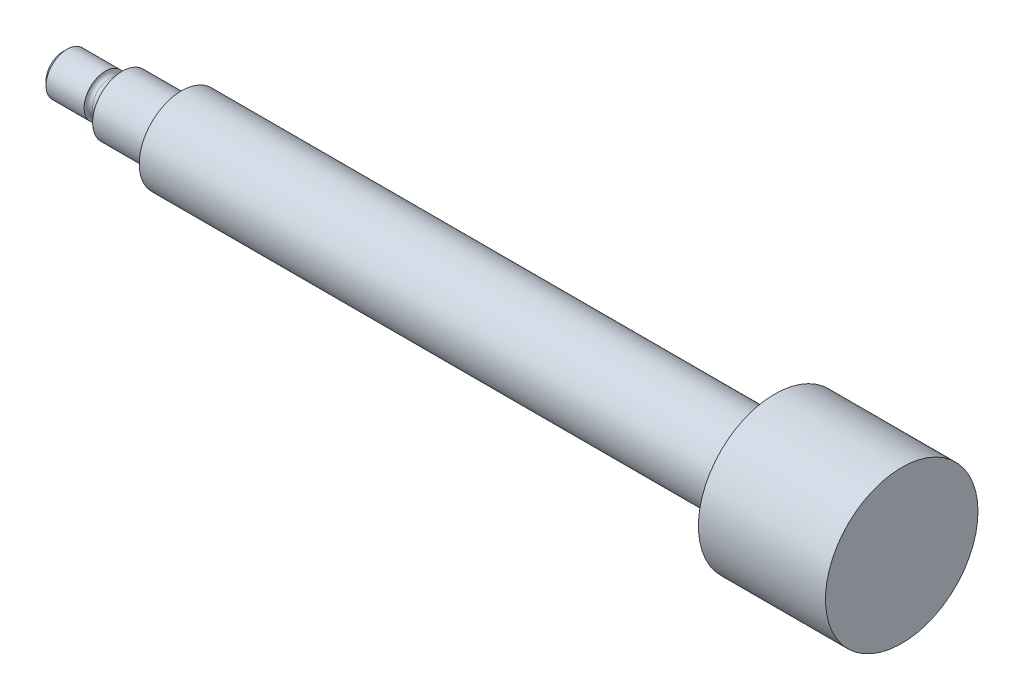
SolidWorks part; units mm, degrees
material "炭素鋼(普通)"
ref_plane "VERT" through (0, 0, 0) normal (0, 0, 1) x (1, 0, 0)
ref_plane "HOR" through (0, 0, 0) normal (0, 1, 0) x (1, 0, 0)
ref_plane "CTR" through (0, 0, 0) normal (1, 0, 0) x (0, 0, -1)
ref_axis "A_X" through (89.95, 0, 0) along (-1, 0, 0)
ref_axis "A_Y" through (0, 9.9, 0) along (0, -1, 0)
ref_axis "A_Z" through (0, 0, 9.9) along (0, 0, -1)
sketch3d "PNT_CG"
  point P0 (0, 0, 0)
sketch "Sketch1" plane through (0, 0, 0) normal (1, 0, 0) x (0, 0, -1)
  circle A0 centre (0, 0) radius 5
  dimension "D1" = 10
extrude "Boss-Extrude1" add sketch "Sketch1" along normal blind 70
cosmetic thread "Cosmetic Thread4" parameters "D1"=67, "D2"=8.3
sketch "Sketch3" plane through (0, 0, 0) normal (-1, 0, 0) x (0, 0, 1)
  circle A0 centre (0, 0) radius 3.5
extrude "Boss-Extrude2" add sketch "Sketch3" along normal blind 7
sketch "Sketch4" plane through (-7, 0, 0) normal (-1, 0, 0) x (0, 0, 1)
  circle A0 centre (0, 0) radius 2.5
extrude "Boss-Extrude3" add sketch "Sketch4" along normal blind 7
cosmetic thread "Cosmetic Thread1" parameters "D2"=4
cosmetic thread "Cosmetic Thread2" parameters "D2"=4
cosmetic thread "Cosmetic Thread3" parameters "D2"=4
sketch "Sketch7" plane through (-7, 0, 0) normal (-1, 0, 0) x (0, 0, 1)
  circle A0 centre (0, 0) radius 2
  dimension "D1" = 4
extrude "Cut-Extrude5" cut sketch "Sketch7" along normal blind 2 flip side to cut contours A0
chamfer "Chamfer1" distance 0.5 angle 45 1 edges at (-14, 0, 2.5)
fillet "Fillet1" radius 0.5 2 edges at (-7, 0, 2) (-9, 0, 2)
sketch "Sketch8" plane through (70, 0, 0) normal (1, 0, 0) x (0, 0, -1)
  circle A0 centre (0, 0) radius 9
  dimension "D1" = 18
extrude "Boss-Extrude4" add sketch "Sketch8" along normal blind 15
